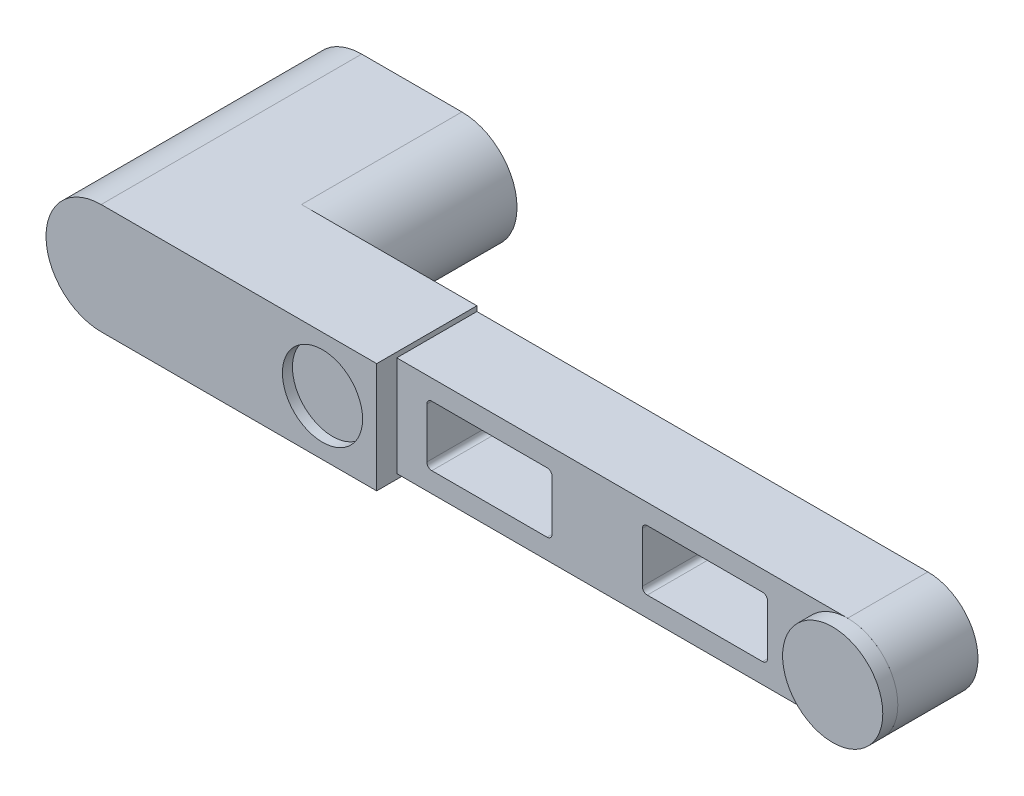
SolidWorks part; units mm, degrees
material "Cast Stainless Steel"
ref_plane "Front Plane" through (0, 0, 0) normal (0, 0, 1) x (1, 0, 0)
ref_plane "Top Plane" through (0, 0, 0) normal (0, 1, 0) x (1, 0, 0)
ref_plane "Right Plane" through (0, 0, 0) normal (1, 0, 0) x (0, 0, -1)
other "Center of Mass"
sketch "Sketch1" plane through (0, 0, 0) normal (1, 0, 0) x (0, 0, -1)
  line L0 (0, 0) -> (-500, 0) construction
  line L5 (-500, 50) -> (-50, 50)
  line L6 (50, -55) -> (-50, -55)
  line L7 (50, -55) -> (50, 55)
  line L8 (50, 55) -> (-50, 55)
  line L9 (-50, -55) -> (-50, 55)
  line L10 (50, -55) -> (-50, 55) construction
  line L11 (50, 55) -> (-50, -55) construction
  line L12 (-500, -50) -> (-50, -50)
  line L13 (0, 0) -> (280, 0)
  line L15 (280, 0) -> (50, 0)
  line L16 (280, 0) -> (280, 55)
  line L17 (280, 55) -> (50, 55)
  line L18 (50, 0) -> (50, 55)
  line L19 (280, 0) -> (50, 0)
  line L20 (280, 0) -> (280, -55)
  line L21 (280, -55) -> (50, -55)
  line L22 (50, 0) -> (50, -55)
  circle A0 centre (-500, 0) radius 50
  dimension "D1" = 100
  dimension "D2" = 110
  dimension "D3" = 100
  dimension "D4" = 500
  dimension "D5" = 280
extrude "Boss-Extrude1" add sketch "Sketch1" along normal blind 100 contours A0 L9 | A0 | L9 L6 L7 L8 | L21 L20 L13 L7 | L16 L17 L7 L13 region at (0, 0, 255.5167) region at (0, 0, 500) region at (0, 52.5, 48.5134) region at (0, 27.5, -165) region at (0, -27.5, -165)
sketch "Sketch2" plane through (0, 55, 0) normal (0, 1, 0) x (1, 0, 0)
  line L0 (0, 280) -> (260, 280)
  line L1 (260, 280) -> (260, 70)
  line L2 (260, 70) -> (100, 70)
  line L4 (0, 280) -> (0, -50)
  line L5 (0, -50) -> (100, -50)
  line L6 (100, -50) -> (100, 280)
  line L7 (100, 280) -> (0, 280)
  line L8 (0, 280) -> (0, -50)
  line L10 (100, -50) -> (100, 280)
  line L11 (100, 280) -> (0, 280)
  line L15 (0, -50) -> (100, -50)
  line M9 (100, -50) -> (100, 280)
  dimension "D2" = 260
  dimension "D3" = 210
  dimension "D1" = 0
extrude "Boss-Extrude2" add sketch "Sketch2" against normal up to surface (110 mm away) contours L2 L1 L0 M9 region at (180, 55, -175) up to face at (50, -55, -115)
sketch "Sketch3" plane through (260, 0, 0) normal (1, 0, 0) x (0, 0, -1)
  line L4 (70, -55) -> (280, -55)
  line L5 (280, -55) -> (280, 55)
  line L6 (280, 55) -> (70, 55)
  line L7 (70, 55) -> (70, -55)
  line L8 (70, -55) -> (280, -55)
  line L9 (280, -55) -> (280, 55)
  line L10 (280, 55) -> (70, 55)
  line L11 (70, 55) -> (70, -55)
  circle A0 centre (125, 0) radius 55
  circle A1 centre (225, 0) radius 55
  line M5 (70, -55) -> (280, -55)
  line M6 (280, -55) -> (280, 55)
  line M7 (280, 55) -> (70, 55)
  line M8 (70, 55) -> (70, -55)
  dimension "D1" = 0
extrude "Cut-Extrude1" cut sketch "Sketch3" against normal up to surface (260 mm away) contours A1 L9 M7 | A1 M5 M6 region at (260, -42.7148, -267.7148) region at (260, 42.7148, -267.7148) up to face at (0, 0, 86.25)
extrude "Cut-Extrude2" cut sketch "Sketch3<3>" against normal up to surface (160 mm away) contours A0 L10 M8 | A0 L11 M5 region at (260, -42.7148, -82.2852) region at (260, 42.7148, -82.2852) up to face at (100, 0, 138.75)
sketch "Sketch3<3>" plane through (260, 0, 0) normal (1, 0, 0) x (0, 0, -1) same geometry as "Sketch3"
ref_plane "Plane1" through (-27.37, 0, 0) normal (-1, 0, 0) x (0, 0, 1)
sketch "Sketch12" plane through (0, 0, 0) normal (-1, 0, 0) x (0, 0, 1)
  line L0 (500, 0) -> (-225, 0) construction
  line L1 (85, 30) -> (200, 30)
  line L2 (80, 25) -> (80, -25)
  line L3 (85, -30) -> (200, -30)
  line L4 (205, 25) -> (205, -25)
  line L5 (250, 30) -> (250, -35.6293) construction
  line L6 (-225, -55) -> (50, -55)
  line L7 (50, -55) -> (50, -50)
  line L8 (50, -50) -> (500, -50)
  line L9 (500, 50) -> (50, 50)
  line L10 (50, 50) -> (50, 55)
  line L11 (50, 55) -> (-225, 55)
  line L12 (-225, -55) -> (50, -55)
  line L13 (50, -55) -> (50, -50)
  line L14 (50, -50) -> (500, -50)
  line L15 (500, 50) -> (50, 50)
  line L16 (50, 50) -> (50, 55)
  line L17 (50, 55) -> (-225, 55)
  line L22 (415, -30) -> (300, -30)
  line L23 (420, 25) -> (420, -25)
  line L24 (295, 25) -> (295, -25)
  line L25 (415, 30) -> (300, 30)
  arc A0 (415, 30) -> (420, 25) centre (415, 25) cw
  arc A1 (415, -30) -> (420, -25) centre (415, -25) ccw
  arc A2 (-225, 55) -> (-225, -55) centre (-225, 0) ccw
  arc A3 (500, -50) -> (500, 50) centre (500, 0) ccw
  arc A4 (-225, 55) -> (-225, -55) centre (-225, 0) ccw
  arc A5 (500, -50) -> (500, 50) centre (500, 0) ccw
  arc A6 (295, 25) -> (300, 30) centre (300, 25) cw
  arc A7 (295, -25) -> (300, -30) centre (300, -25) ccw
  arc A8 (205, 25) -> (200, 30) centre (200, 25) ccw
  arc A9 (205, -25) -> (200, -30) centre (200, -25) cw
  arc A10 (85, 30) -> (80, 25) centre (85, 25) ccw
  arc A11 (80, -25) -> (85, -30) centre (85, -25) ccw
  point P22 (420, 30)
  point P25 (420, -30)
  point P28 (295, 30)
  point P31 (295, -30)
  point P36 (205, 30)
  point P39 (205, -30)
  point P42 (80, 30)
  point P45 (80, -30)
  dimension "D6" = 5
  dimension "D2" = 125
  dimension "D3" = 60
  dimension "D4" = 80
  dimension "D5" = 45
  dimension "D1" = 0
extrude "Cut-Extrude3" cut sketch "Sketch12" against normal up to surface (100 mm away) contours L4 L1 L2 L3 | L23 L25 L24 L22 region at (0, 0, 142.5) region at (0, 0, 357.5) up to face at (100, 0, 131.875)
sketch "Sketch13" plane through (100, 0, 0) normal (1, 0, 0) x (0, 0, -1)
  line L0 (-50, -48) -> (125, -48)
  line L1 (125, -48) -> (225, -48)
  line L2 (125, -55) -> (225, -55)
  line L3 (225, 55) -> (125, 55)
  line L4 (125, -55) -> (225, -55)
  line L5 (225, 55) -> (125, 55)
  line L6 (-50, -55) -> (125, -55)
  line L7 (125, 55) -> (-50, 55)
  line L8 (-50, 55) -> (-50, 50)
  line L9 (-50, 50) -> (-500, 50)
  line L10 (-500, -50) -> (-50, -50)
  line L11 (-50, -50) -> (-50, -55)
  line L12 (-50, -55) -> (125, -55)
  line L13 (125, 55) -> (-50, 55)
  line L14 (-50, 55) -> (-50, 50)
  line L15 (-50, 50) -> (-500, 50)
  line L16 (-500, -50) -> (-50, -50)
  line L17 (-50, -50) -> (-50, -55)
  line L18 (225, 48) -> (125, 48)
  line L19 (125, 48) -> (-50, 48)
  line L20 (-43, 55) -> (-43, 50)
  line L21 (-50, 43) -> (-500, 43)
  line L22 (-50, -55) -> (225, -55)
  line L23 (-50, -50) -> (-50, -55)
  line L24 (-500, -50) -> (-50, -50)
  line L25 (-50, 50) -> (-500, 50)
  line L26 (-50, 55) -> (-50, 50)
  line L27 (225, 55) -> (-50, 55)
  line L28 (-50, -55) -> (225, -55)
  line L29 (-50, -50) -> (-50, -55)
  line L30 (-500, -50) -> (-50, -50)
  line L31 (-50, 50) -> (-500, 50)
  line L32 (-50, 55) -> (-50, 50)
  line L33 (225, 55) -> (-50, 55)
  line L34 (-500, -43) -> (-50, -43)
  line L35 (-43, -50) -> (-43, -55)
  line L36 (-50, -48) -> (225, -48)
  line L37 (225, 48) -> (-50, 48)
  line L38 (-43, -50) -> (-43, -55)
  line L39 (-500, -43) -> (-50, -43)
  line L40 (-50, 43) -> (-500, 43)
  line L41 (-43, 55) -> (-43, 50)
  line L42 (-50, -48) -> (-50, -43)
  line L43 (-50, 43) -> (-50, 48)
  arc A0 (225, -48) -> (225, 48) centre (225, 0) ccw
  arc A1 (225, -48) -> (225, 48) centre (225, 0) ccw
  arc A2 (125, 55) -> (125, -55) centre (125, 0) ccw
  arc A3 (-500, 50) -> (-500, -50) centre (-500, 0) ccw
  arc A5 (-500, 50) -> (-500, -50) centre (-500, 0) ccw
  arc A6 (125, 55) -> (125, -55) centre (125, 0) ccw
  arc A7 (225, -55) -> (225, 55) centre (225, 0) ccw
  arc A8 (-500, 43) -> (-500, -43) centre (-500, 0) ccw
  arc A9 (225, -55) -> (225, 55) centre (225, 0) ccw
  arc A10 (225, -55) -> (225, 55) centre (225, 0) ccw
  arc A11 (-500, 50) -> (-500, -50) centre (-500, 0) ccw
  arc A12 (225, -55) -> (225, 55) centre (225, 0) ccw
  arc A13 (-500, 50) -> (-500, -50) centre (-500, 0) ccw
  arc A14 (-500, 43) -> (-500, -43) centre (-500, 0) ccw
  dimension "D1" = 0
  dimension "D2" = 0
  dimension "D3" = 0
  dimension "D4" = 7
move or copy body "Body-Move/Copy1" bodies to move or copy 113 copy no rotation origin (130, 0, 135) rotation axis (0, 1, 0) rotation angle 86
sketch "Sketch15" plane through (-17.83, 0, 254.9802) normal (-0.0698, 0, 0.9976) x (0.9976, 0, 0.0698)
  line L6 (-220.8995, -55) -> (54.1005, -55)
  line L7 (54.1005, -55) -> (54.1005, -50)
  line L8 (54.1005, -50) -> (504.1005, -50)
  line L9 (504.1005, 50) -> (54.1005, 50)
  line L10 (54.1005, 50) -> (54.1005, 55)
  line L11 (54.1005, 55) -> (-220.8995, 55)
  line L12 (-220.8995, -55) -> (54.1005, -55)
  line L13 (54.1005, -55) -> (54.1005, -50)
  line L14 (54.1005, -50) -> (504.1005, -50)
  line L15 (504.1005, 50) -> (54.1005, 50)
  line L16 (54.1005, 50) -> (54.1005, 55)
  line L17 (54.1005, 55) -> (-220.8995, 55)
  circle A0 centre (0, 0) radius 40
  arc A2 (-220.8995, 55) -> (-220.8995, -55) centre (-220.8995, 0) ccw
  arc A3 (504.1005, -50) -> (504.1005, 50) centre (504.1005, 0) ccw
  arc A4 (-220.8995, 55) -> (-220.8995, -55) centre (-220.8995, 0) ccw
  arc A5 (504.1005, -50) -> (504.1005, 50) centre (504.1005, 0) ccw
  point P0 (0, 0)
  dimension "D2" = 80
  dimension "D1" = 0
extrude "Cut-Extrude4" cut sketch "Sketch15" against normal blind 10 contours A0 region at (-17.83, 0, 254.9802)
sketch "Sketch16" plane through (-17.83, 0, 254.9802) normal (-0.0698, 0, 0.9976) x (0.9976, 0, 0.0698)
  point P0 (0, 0)
move or copy body "Body-Move/Copy2" bodies to move or copy 117 copy no translate (17.83, 0, -254.9802)
sketch "Sketch17" plane through (0, 0, 0) normal (-0.0698, 0, 0.9976) x (0.9976, 0, 0.0698)
  line L0 (54.1005, 50) -> (54.1005, -50)
  line L6 (-220.8995, -55) -> (54.1005, -55)
  line L7 (54.1005, -55) -> (54.1005, -50)
  line L8 (54.1005, -50) -> (504.1005, -50)
  line L9 (504.1005, 50) -> (54.1005, 50)
  line L10 (54.1005, 50) -> (54.1005, 55)
  line L11 (54.1005, 55) -> (-220.8995, 55)
  line L12 (-220.8995, -55) -> (54.1005, -55)
  line L13 (54.1005, -55) -> (54.1005, -50)
  line L14 (54.1005, -50) -> (504.1005, -50)
  line L15 (504.1005, 50) -> (54.1005, 50)
  line L16 (54.1005, 50) -> (54.1005, 55)
  line L17 (54.1005, 55) -> (-220.8995, 55)
  arc A2 (-220.8995, 55) -> (-220.8995, -55) centre (-220.8995, 0) ccw
  arc A3 (504.1005, -50) -> (504.1005, 50) centre (504.1005, 0) ccw
  arc A4 (-220.8995, 55) -> (-220.8995, -55) centre (-220.8995, 0) ccw
  arc A5 (504.1005, -50) -> (504.1005, 50) centre (504.1005, 0) ccw
  line M10 (204.1005, -30) -> (89.1005, -30)
  arc M11 (89.1005, -30) -> (84.1005, -25) centre (89.1005, -25) cw
  line M12 (84.1005, -25) -> (84.1005, 25)
  arc M13 (84.1005, 25) -> (89.1005, 30) centre (89.1005, 25) cw
  line M14 (89.1005, 30) -> (204.1005, 30)
  arc M15 (204.1005, 30) -> (209.1005, 25) centre (204.1005, 25) cw
  line M16 (209.1005, 25) -> (209.1005, -25)
  arc M17 (209.1005, -25) -> (204.1005, -30) centre (204.1005, -25) cw
  line M18 (419.1005, -30) -> (304.1005, -30)
  arc M19 (304.1005, -30) -> (299.1005, -25) centre (304.1005, -25) cw
  line M20 (299.1005, -25) -> (299.1005, 25)
  arc M21 (299.1005, 25) -> (304.1005, 30) centre (304.1005, 25) cw
  line M22 (304.1005, 30) -> (419.1005, 30)
  arc M23 (419.1005, 30) -> (424.1005, 25) centre (419.1005, 25) cw
  line M24 (424.1005, 25) -> (424.1005, -25)
  arc M25 (424.1005, -25) -> (419.1005, -30) centre (419.1005, -25) cw
  line M29 (54.1005, -50) -> (504.1005, -50)
  arc M30 (504.1005, -50) -> (504.1005, 50) centre (504.1005, 0) ccw
  line M31 (504.1005, 50) -> (54.1005, 50)
  dimension "D1" = 0
extrude "Cut-Extrude5" cut sketch "Sketch17" against normal blind 20 contours L0 M31 M29 M30 M25 M18 M19 M20 M21 M22 M23 M24 M17 M10 M11 M12 M13 M14 M15 M16 region at (278.4206, 44.901, 19.4691)
sketch "Sketch18" plane through (1.3951, 0, -19.9513) normal (-0.0698, 0, 0.9976) x (0.9976, 0, 0.0698)
  line L3 (504.1005, 50) -> (54.1005, 50)
  line L4 (54.1005, 50) -> (54.1005, -50)
  line L5 (54.1005, -50) -> (504.1005, -50)
  line L6 (504.1005, 50) -> (54.1005, 50)
  line L7 (54.1005, 50) -> (54.1005, -50)
  line L8 (54.1005, -50) -> (504.1005, -50)
  circle A0 centre (504.1005, 0) radius 50
  arc A1 (504.1005, -50) -> (504.1005, 50) centre (504.1005, 0) ccw
  arc A2 (504.1005, -50) -> (504.1005, 50) centre (504.1005, 0) ccw
  arc M24 (504.1005, -50) -> (504.1005, 50) centre (504.1005, 0) ccw
  dimension "D1" = 0
extrude "Boss-Extrude3" add sketch "Sketch18" along normal blind 15 separate body contours A0 M24 region at (504.2676, 0, 15.213)
move or copy body "Body-Move/Copy6" bodies to move or copy 119 120 copy no rotation origin (0, 0, 0) rotation axis (0, 1, 0) rotation angle 4
ref_plane "Plane2" through (0, 0, 27.37) normal (0, 0, 1) x (1, 0, 0)
ref_axis "Axis1" through (0, 0, -10) along (0, 0, 1)
ref_point "Point1"
move or copy body "Body-Move/Copy7" bodies to move or copy 127 128 copy no translate (0, 0, -27.37)
